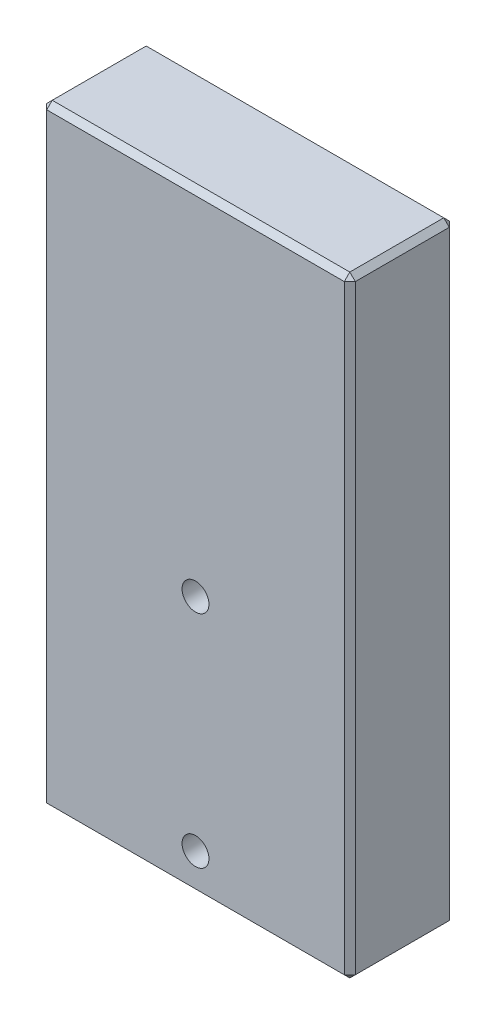
SolidWorks part; units mm, degrees
ref_plane "Front Plane" through (0, 0, 0) normal (0, 0, 1) x (1, 0, 0)
ref_plane "Top Plane" through (0, 0, 0) normal (0, 1, 0) x (1, 0, 0)
ref_plane "Right Plane" through (0, 0, 0) normal (1, 0, 0) x (0, 0, -1)
sketch "Sketch1" plane through (0, 0, 0) normal (0, 0, 1) x (1, 0, 0)
  line L1 (0, 0) -> (28, 0)
  line L2 (0, 0) -> (0, 55.475)
  line L3 (0, 55.475) -> (28, 55.475)
  line L4 (28, 0) -> (28, 55.475)
  dimension "D1" = 28
  dimension "D2" = 55.475
extrude "Boss-Extrude1" add sketch "Sketch1" along normal blind 9.525
sketch "Sketch2" plane through (0, 0, 0) normal (0, -1, 0) x (1, 0, 0)
  line L0 (0, 0) -> (28, 0) construction
  line L1 (0, 9.525) -> (0, 0) construction
  circle A0 centre (5, 4.7625) radius 1.2195
  circle A3 centre (23, 4.7625) radius 1.2195
  dimension "D1" = 2.439
  dimension "D6" = 2.439
  dimension "D2" = 4.7625
  dimension "D3" = 5
  dimension "D4" = 18
extrude "Cut-Extrude1" cut sketch "Sketch2" against normal blind 20
sketch "Sketch3" plane through (0, 0, 9.525) normal (0, 0, 1) x (1, 0, 0)
  line L0 (22.85, 65) -> (5.15, 65)
  line L1 (5.15, 65) -> (5.15, 0)
  line L2 (5.15, 0) -> (22.85, 0)
  line L3 (22.85, 0) -> (22.85, 65)
  line L4 (0, 55.475) -> (0, 0) construction
  circle A0 centre (14, 3.475) radius 1.7
  circle A1 centre (14, 3.475) radius 1.2195
  circle A2 centre (14, 23.475) radius 1.7
  circle A3 centre (14, 23.475) radius 1.2195
  dimension "D6" = 2.439
  dimension "D7" = 3.4
  dimension "D8" = 3.4
  dimension "D9" = 2.439
  dimension "D1" = 3.475
  dimension "D2" = 23.475
  dimension "D3" = 8.85
  dimension "D4" = 65
  dimension "D5" = 17.7
  dimension "D10" = 0
  dimension "D11" = 14
extrude "Cut-Extrude2" cut sketch "Sketch3" against normal through all contours A3 | A1 region at (14, 3.475, 9.525) region at (14, 23.475, 9.525)
chamfer "Chamfer1" distance 0.5 angle 45 12 edges at (14, 0, 0) (28, 0, 4.7625) (28, 27.7375, 0) (14, 55.475, 0) (28, 55.475, 4.7625) (28, 27.7375, 9.525) (14, 55.475, 9.525) (14, 0, 9.525) (0, 0, 4.7625) (0, 27.7375, 0) (0, 55.475, 4.7625) (0, 27.7375, 9.525)
